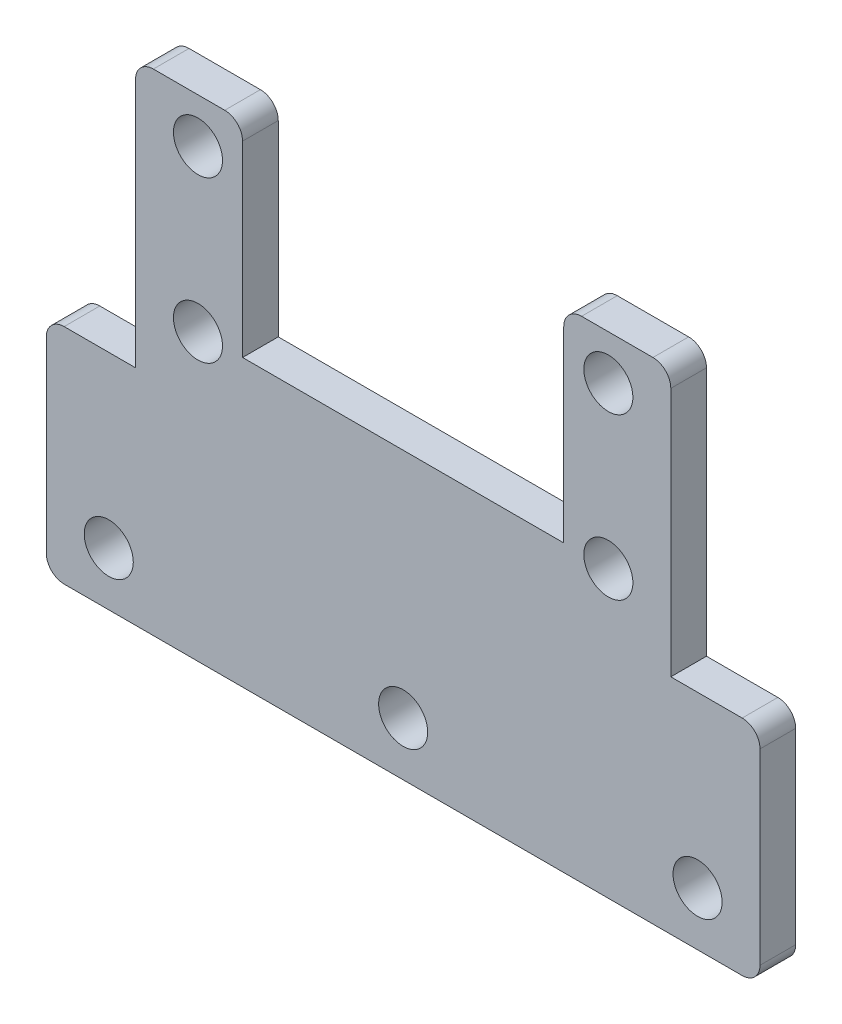
SolidWorks part; units mm, degrees
ref_plane "Спереди" through (0, 0, 0) normal (0, 0, 1) x (1, 0, 0)
ref_plane "Сверху" through (0, 0, 0) normal (0, 1, 0) x (1, 0, 0)
ref_plane "Справа" through (0, 0, 0) normal (1, 0, 0) x (0, 0, -1)
sketch "Эскиз1" plane through (0, 0, 0) normal (0, 0, 1) x (1, 0, 0)
  line L0 (18, 0) -> (-18, 0)
  line L1 (-18, 0) -> (-18, 23)
  line L2 (-18, 23) -> (-30, 23)
  line L3 (-30, 23) -> (-30, -7)
  line L4 (-40, -32) -> (40, -32)
  line L5 (0, 0) -> (0, -32) construction
  line L6 (-30, -7) -> (-40, -7)
  line L7 (-40, -7) -> (-40, -32)
  line L8 (40, -7) -> (40, -32)
  line L9 (30, -7) -> (40, -7)
  line L10 (30, 23) -> (30, -7)
  line L11 (18, 23) -> (30, 23)
  line L12 (18, 0) -> (18, 23)
  circle A0 centre (-23, 18) radius 2.75
  circle A1 centre (-23, 0) radius 2.75
  circle A2 centre (-33, -26) radius 2.75
  circle A3 centre (0, -26) radius 2.75
  circle A4 centre (33, -26) radius 2.75
  circle A5 centre (23, 18) radius 2.75
  circle A6 centre (23, 0) radius 2.75
  dimension "D2" = 18
  dimension "D3" = 25
  dimension "D7" = 6
  dimension "D8" = 33
  dimension "D9" = 5.5
  dimension "D1" = 7
  dimension "D4" = 55
  dimension "D5" = 12
  dimension "D6" = 7
  dimension "D10" = 60
  dimension "D11" = 80
  dimension "D12" = 7
extrude "Бобышка-Вытянуть1" add sketch "Эскиз1" along normal blind 4
fillet "Скругление1" radius 2 8 edges at (-18, 23, 2) (18, 23, 2) (30, 23, 2) (40, -7, 2) (40, -32, 2) (-40, -32, 2) (-40, -7, 2) (-30, 23, 2)
